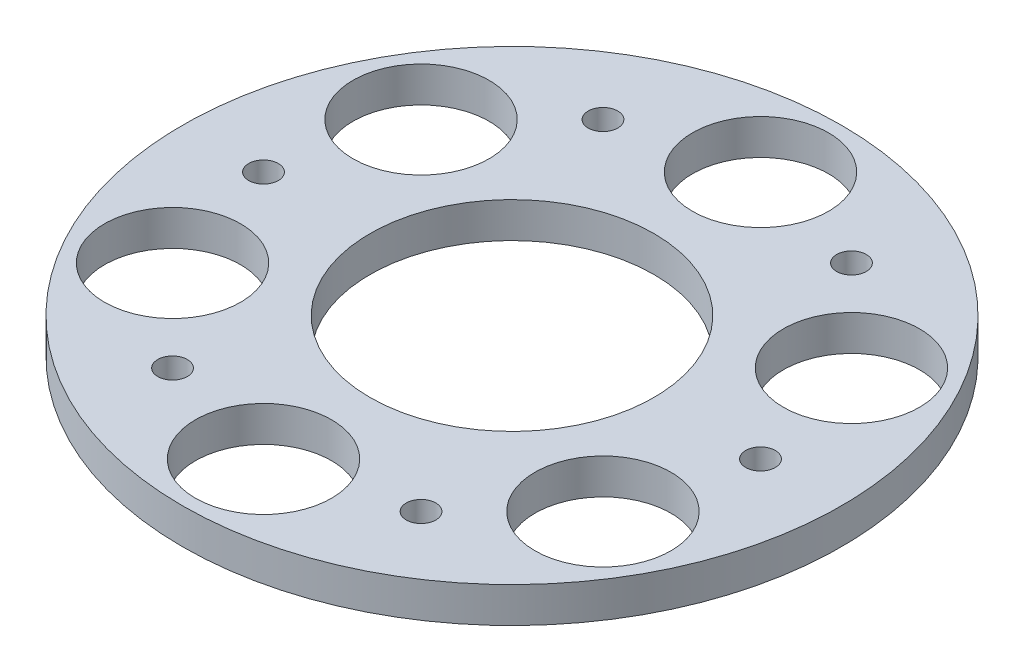
SolidWorks part; units mm, degrees
ref_plane "Płaszczyzna przednia" through (0, 0, 0) normal (0, 0, 1) x (1, 0, 0)
ref_plane "Płaszczyzna górna" through (0, 0, 0) normal (0, 1, 0) x (1, 0, 0)
ref_plane "Płaszczyzna prawa" through (0, 0, 0) normal (1, 0, 0) x (0, 0, -1)
sketch "Sketch1" plane through (0, 0, 0) normal (0, 1, 0) x (1, 0, 0)
  line L0 (0, 0) -> (0, 21) construction
  line L1 (0, 0) -> (10.5, 18.1865) construction
  circle A0 centre (0, 0) radius 27.85
  circle A1 centre (0, 0) radius 21 construction
  circle A2 centre (0, 21) radius 5.75
  circle A3 centre (18.1865, 10.5) radius 5.75
  circle A4 centre (18.1865, -10.5) radius 5.75
  circle A5 centre (0, -21) radius 5.75
  circle A6 centre (-18.1865, -10.5) radius 5.75
  circle A7 centre (-18.1865, 10.5) radius 5.75
  circle A8 centre (10.5, 18.1865) radius 1.25
  circle A9 centre (21, 0) radius 1.25
  circle A10 centre (10.5, -18.1865) radius 1.25
  circle A11 centre (-10.5, -18.1865) radius 1.25
  circle A12 centre (-21, 0) radius 1.25
  circle A13 centre (-10.5, 18.1865) radius 1.25
  circle A14 centre (0, 0) radius 12
  point P18 (0, 0)
  point P31 (0, 0)
  dimension "D1" = 55.7
  dimension "D2" = 42
  dimension "D3" = 11.5
  dimension "D6" = 2.5
  dimension "D8" = 24
  dimension "D5" = 30
  dimension "D4" = 6
  dimension "D7" = 6
extrude "Boss-Extrude1" add sketch "Sketch1" along normal blind 3
